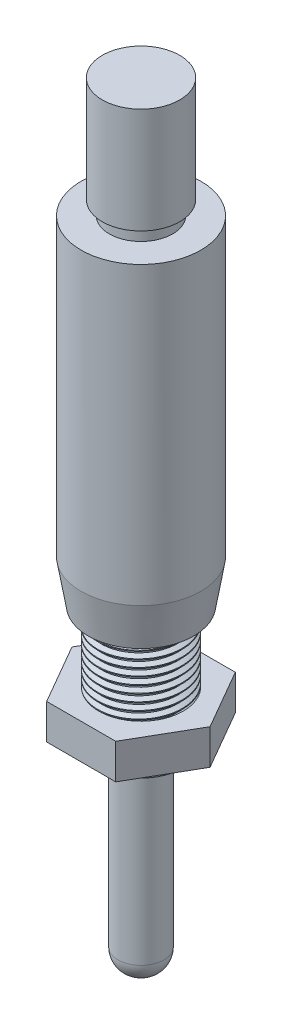
SolidWorks part; units mm, degrees
ref_plane "前视基准面" through (0, 0, 0) normal (0, 0, 1) x (1, 0, 0)
ref_plane "上视基准面" through (0, 0, 0) normal (0, 1, 0) x (1, 0, 0)
ref_plane "右视基准面" through (0, 0, 0) normal (1, 0, 0) x (0, 0, -1)
sketch "草图1" plane through (0, 0, 0) normal (0, 1, 0) x (1, 0, 0)
  circle A0 centre (0, 0) radius 3.25
  dimension "D1" = 6.5
extrude "凸台-拉伸2" add sketch "草图1" along normal blind 28
fillet "圆角1" radius 3 1 edges at (0, 0, 3.25)
sketch "草图2" plane through (0, 28, 0) normal (0, 1, 0) x (1, 0, 0)
  circle A0 centre (0, 0) radius 6
  dimension "D1" = 12
extrude "凸台-拉伸3" add sketch "草图2" along normal blind 2
sketch "草图3" plane through (0, 30, 0) normal (0, 1, 0) x (1, 0, 0)
  line L1 (-9.815, 0) -> (-4.9075, -8.5)
  line L2 (-4.9075, -8.5) -> (4.9075, -8.5)
  line L3 (4.9075, -8.5) -> (9.815, 0)
  line L4 (9.815, 0) -> (4.9075, 8.5)
  line L5 (4.9075, 8.5) -> (-4.9075, 8.5)
  line L6 (-4.9075, 8.5) -> (-9.815, 0)
  circle A0 centre (0, 0) radius 8.5 construction
extrude "凸台-拉伸4" add sketch "草图3" along normal blind 5
sketch "草图4" plane through (0, 35, 0) normal (0, 1, 0) x (1, 0, 0)
  circle A0 centre (0, 0) radius 6
extrude "凸台-拉伸5" add sketch "草图4" along normal blind 10
sketch "草图5" plane through (0, 45, 0) normal (0, 1, 0) x (1, 0, 0)
  circle A0 centre (0, 0) radius 7.5
ref_plane "基准面4" through (0, 51, 0) normal (0, 1, 0) x (1, 0, 0)
sketch "草图6" plane through (0, 51, 0) normal (0, 1, 0) x (1, 0, 0)
  circle A0 centre (0, 0) radius 8.5
loft "放样1" add profiles "草图5", "草图6" connector at (0, 45, 7.5) connector at (-0.0397, 51, 8.4999)
sketch "草图7" plane through (0, 51, 0) normal (0, 1, 0) x (1, 0, 0)
  circle A0 centre (0, 0) radius 8.5
extrude "凸台-拉伸6" add sketch "草图7" along normal blind 42
sketch "草图8" plane through (0, 93, 0) normal (0, 1, 0) x (1, 0, 0)
  circle A0 centre (0, 0) radius 4.5
extrude "凸台-拉伸7" add sketch "草图8" along normal blind 2
sketch "草图9" plane through (0, 95, 0) normal (0, 1, 0) x (1, 0, 0)
  circle A0 centre (0, 0) radius 5.5
extrude "凸台-拉伸8" add sketch "草图9" along normal blind 15
thread "螺纹线1" pitch 1.0583 method cut profile "螺纹线轮廓1" start angle 0, offset 0, length 16, pitch 1.0583, diameter 12
ref_plane "基准面5" through (6, 28, 0) normal (0, 0, 1) x (1, 0, 0)
sketch "螺纹线轮廓1" plane through (6, 28, 0) normal (0, 0, 1) x (1, 0, 0)
  line L0 (0, 0) -> (0, 1.0583) construction
  line L11 (0, 0) -> (0, 0.926)
  line L12 (0, 0.926) -> (-0.5728, 0.5953)
  line L13 (-0.5728, 0.5953) -> (-0.5728, 0.3307)
  line L15 (-0.5728, 0.3307) -> (0, 0)
  line L17 (-0.5728, 0.463) -> (0, 0.463) construction
  point P2 (0, 0)
  dimension "Pitch" = 1.0583
  dimension "Profile_Angle" = 60
  dimension "Profile_Land" = 0.2646
  dimension "Profile_Height" = 0.5728
